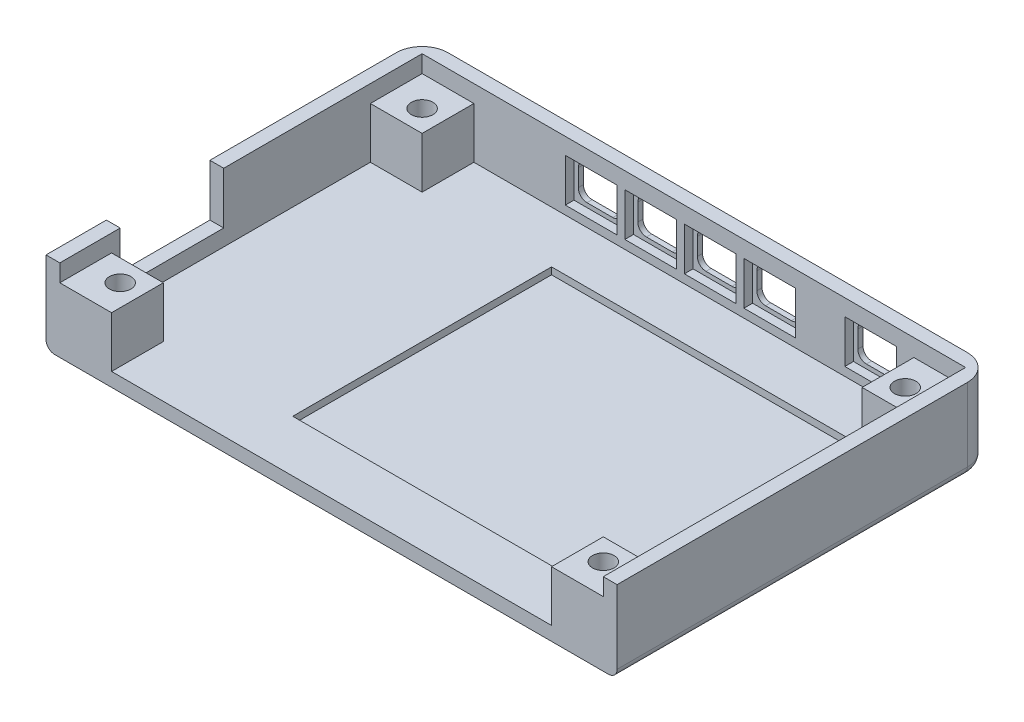
SolidWorks part; units mm, degrees
ref_plane "前视基准面" through (0, 0, 0) normal (0, 0, 1) x (1, 0, 0)
ref_plane "上视基准面" through (0, 0, 0) normal (0, 1, 0) x (1, 0, 0)
ref_plane "右视基准面" through (0, 0, 0) normal (1, 0, 0) x (0, 0, -1)
sketch "草图1" plane through (0, 0, 0) normal (0, 1, 0) x (1, 0, 0)
  line L1 (-31.5, -21) -> (31.5, -21)
  line L2 (-31.5, -21) -> (-31.5, 21)
  line L3 (-31.5, 21) -> (31.5, 21)
  line L4 (31.5, -21) -> (31.5, 21)
  line L5 (-31.5, -21) -> (31.5, 21) construction
  line L6 (-31.5, 21) -> (31.5, -21) construction
  point P0 (0, 0)
  dimension "D1" = 63
  dimension "D2" = 42
extrude "底" add sketch "草图1" against normal blind 1.6
sketch "草图2" plane through (0, 0, 0) normal (0, 1, 0) x (1, 0, 0)
  line L1 (-10.5, -15) -> (31.5, -15)
  line L2 (-10.5, -15) -> (-10.5, 15)
  line L3 (-10.5, 15) -> (31.5, 15)
  line L4 (31.5, -15) -> (31.5, 15)
  line L5 (-10.5, -15) -> (31.5, 15) construction
  line L6 (-10.5, 15) -> (31.5, -15) construction
  line L7 (31.5, 21) -> (-31.5, 21) construction
  line L8 (-31.5, -21) -> (31.5, -21) construction
  line L9 (31.5, -21) -> (31.5, 21) construction
  point P0 (0, 0)
  dimension "D1" = 42
  dimension "D2" = 6
  dimension "D3" = 0
  dimension "D4" = 6
extrude "电池槽" cut sketch "草图2" against normal blind 0.8
sketch "草图4" plane through (0, -1.6, 0) normal (0, -1, 0) x (-1, 0, 0)
  line L0 (-31.5, 21) -> (-31.5, -21)
  line L1 (-31.5, 21) -> (-33.1, 21)
  line L2 (-31.5, -21) -> (-33.1, -21)
  line L3 (-33.1, 21) -> (-33.1, -21)
  line L4 (31.5, 21) -> (31.5, -21)
  line L5 (31.5, 21) -> (33.1, 21)
  line L6 (31.5, -21) -> (33.1, -21)
  line L7 (33.1, 21) -> (33.1, -21)
  dimension "D1" = 1.6
  dimension "D2" = 1.6
extrude "侧边" add sketch "草图4" against normal blind 9.5
sketch "草图5" plane through (0, 0, 0) normal (0, 1, 0) x (1, 0, 0)
  line L0 (-31.5, 21) -> (-31.5, 15)
  line L1 (-31.5, 21) -> (-25.5, 21)
  line L2 (-31.5, 15) -> (-25.5, 15)
  line L3 (-25.5, 21) -> (-25.5, 15)
  line L4 (-31.5, 21) -> (-31.5, -21) construction
  line L5 (25.5, 21) -> (25.5, 15)
  line L6 (25.5, 21) -> (31.5, 21)
  line L7 (25.5, 15) -> (31.5, 15)
  line L8 (31.5, 21) -> (31.5, 15)
  line L9 (-31.5, -15) -> (-31.5, -21)
  line L10 (-31.5, -15) -> (-25.5, -15)
  line L11 (-31.5, -21) -> (-25.5, -21)
  line L12 (-25.5, -15) -> (-25.5, -21)
  line L13 (25.5, -15) -> (25.5, -21)
  line L14 (25.5, -15) -> (31.5, -15)
  line L15 (25.5, -21) -> (31.5, -21)
  line L16 (31.5, -15) -> (31.5, -21)
  dimension "D1" = 6
  dimension "D2" = 6
  dimension "D3" = 6
  dimension "D4" = 6
extrude "螺丝固定" add sketch "草图5" along normal offset from surface (5.9 mm away) 2 up to face at (-32.3, 7.9, 0)
sketch "草图6" plane through (0, 7.9, 0) normal (0, 1, 0) x (1, 0, 0)
  line L0 (-25.5, 15) -> (-25.5, 21) construction
  line L1 (-31.5, 15) -> (-25.5, 15) construction
  circle A0 centre (-28, 17.5) radius 1.25
  circle A1 centre (28, 17.5) radius 1.25
  circle A2 centre (28, -17.5) radius 1.25
  circle A3 centre (-28, -17.5) radius 1.25
  dimension "D1" = 2.5
  dimension "D2" = 2.5
  dimension "D3" = 2.5
  dimension "D4" = 2
  dimension "D5" = 2
extrude "螺丝孔" cut sketch "草图6" against normal up to surface (7.9 mm away) up to face at (-7, 0, 0)
sketch "草图8" plane through (0, 0, 0) normal (0, 1, 0) x (1, 0, 0)
  line L0 (25.5, 21) -> (25.5, 15) construction
  line L1 (-30.5, 20) -> (-25.5, 20)
  line L2 (-30.5, 20) -> (-30.5, 15)
  line L3 (-30.5, 15) -> (-25.5, 15)
  line L4 (-25.5, 20) -> (-25.5, 15)
  line L5 (-30.5, 20) -> (-25.5, 15) construction
  line L6 (-30.5, 15) -> (-25.5, 20) construction
  line L7 (30.5, 20) -> (25.5, 20)
  line L8 (30.5, 20) -> (30.5, 15)
  line L9 (30.5, 15) -> (25.5, 15)
  line L10 (25.5, 20) -> (25.5, 15)
  line L11 (30.5, 20) -> (25.5, 15) construction
  line L12 (30.5, 15) -> (25.5, 20) construction
  line L14 (-30.5, -20) -> (-25.5, -20)
  line L15 (-30.5, -20) -> (-30.5, -15)
  line L16 (-30.5, -15) -> (-25.5, -15)
  line L17 (-25.5, -20) -> (-25.5, -15)
  line L18 (-30.5, -20) -> (-25.5, -15) construction
  line L19 (-30.5, -15) -> (-25.5, -20) construction
  line L20 (30.5, -20) -> (25.5, -20)
  line L21 (30.5, -20) -> (30.5, -15)
  line L22 (30.5, -15) -> (25.5, -15)
  line L23 (25.5, -20) -> (25.5, -15)
  line L24 (30.5, -20) -> (25.5, -15) construction
  line L25 (30.5, -15) -> (25.5, -20) construction
  circle A0 centre (28, 17.5) radius 1.25 construction
  circle A1 centre (28, -17.5) radius 1.25 construction
  circle A2 centre (-28, -17.5) radius 1.25 construction
  circle A3 centre (-28, 17.5) radius 1.25 construction
  circle A4 centre (28, 17.5) radius 1.25 construction
  circle A5 centre (28, -17.5) radius 1.25 construction
  circle A6 centre (-28, -17.5) radius 1.25 construction
  circle A7 centre (-28, 17.5) radius 1.25 construction
sketch "草图9" plane through (0, 0, -21) normal (0, 0, -1) x (-1, 0, 0)
  line L0 (-33.1, 7.9) -> (-33.1, -1.6)
  line L1 (-33.1, 7.9) -> (33.1, 7.9)
  line L2 (-33.1, -1.6) -> (33.1, -1.6)
  line L3 (33.1, 7.9) -> (33.1, -1.6)
extrude "凸台-拉伸4" add sketch "草图9" along normal blind 1.6
sketch "草图10" plane through (0, 0, -21) normal (0, 0, 1) x (1, 0, 0)
  line L1 (17.5, 1) -> (23.5, 1)
  line L2 (17.5, 1) -> (17.5, 6)
  line L3 (17.5, 6) -> (23.5, 6)
  line L4 (23.5, 1) -> (23.5, 6)
  line L5 (17.5, 1) -> (23.5, 6) construction
  line L6 (17.5, 6) -> (23.5, 1) construction
  line L7 (25.5, 0) -> (-25.5, 0) construction
  line L8 (25.5, 5.9) -> (25.5, 0) construction
  line L9 (5.8, 1) -> (11.8, 1)
  line L10 (5.8, 1) -> (5.8, 6)
  line L11 (5.8, 6) -> (11.8, 6)
  line L12 (11.8, 1) -> (11.8, 6)
  line L13 (5.8, 1) -> (11.8, 6) construction
  line L14 (5.8, 6) -> (11.8, 1) construction
  line L15 (-1.1, 1) -> (4.9, 1)
  line L16 (-1.1, 1) -> (-1.1, 6)
  line L17 (-1.1, 6) -> (4.9, 6)
  line L18 (4.9, 1) -> (4.9, 6)
  line L19 (-1.1, 1) -> (4.9, 6) construction
  line L20 (-1.1, 6) -> (4.9, 1) construction
  line L21 (-8, 1) -> (-2, 1)
  line L22 (-8, 1) -> (-8, 6)
  line L23 (-8, 6) -> (-2, 6)
  line L24 (-2, 1) -> (-2, 6)
  line L25 (-8, 1) -> (-2, 6) construction
  line L26 (-8, 6) -> (-2, 1) construction
  line L27 (-14.9, 1) -> (-8.9, 1)
  line L28 (-14.9, 1) -> (-14.9, 6)
  line L29 (-14.9, 6) -> (-8.9, 6)
  line L30 (-8.9, 1) -> (-8.9, 6)
  line L31 (-14.9, 1) -> (-8.9, 6) construction
  line L32 (-14.9, 6) -> (-8.9, 1) construction
  point P0 (20.5, 3.5)
  point P11 (8.8, 3.5)
  point P16 (1.9, 3.5)
  point P21 (-5, 3.5)
  point P26 (-11.9, 3.5)
  dimension "D1" = 6
  dimension "D2" = 5
  dimension "D3" = 5
  dimension "D4" = 3.5
  dimension "D5" = 2
  dimension "D6" = 4
extrude "按键底" cut sketch "草图10" against normal blind 1
sketch "草图12" plane through (0, 0, -22) normal (0, 0, 1) x (1, 0, 0)
  line L0 (17.5, 6) -> (23.5, 1) construction
  line L1 (6.3, 2.5) -> (6.3, 4.5)
  line L2 (19, 1.5) -> (22, 1.5)
  line L3 (18, 2.5) -> (18, 4.5)
  line L4 (23.5, 1) -> (23.5, 6)
  line L5 (23.5, 6) -> (17.5, 6)
  line L6 (17.5, 6) -> (17.5, 1)
  line L7 (17.5, 1) -> (23.5, 1)
  line L8 (23.5, 1) -> (23.5, 6) construction
  line L9 (23.5, 6) -> (17.5, 6) construction
  line L10 (17.5, 6) -> (17.5, 1) construction
  line L11 (17.5, 1) -> (23.5, 1) construction
  line L12 (19, 5.5) -> (22, 5.5)
  line L13 (23, 2.5) -> (23, 4.5)
  line L14 (18, 1.5) -> (23, 5.5) construction
  line L15 (18, 5.5) -> (23, 1.5) construction
  line L16 (7.3, 1.5) -> (10.3, 1.5)
  line L17 (7.3, 5.5) -> (10.3, 5.5)
  line L18 (11.3, 2.5) -> (11.3, 4.5)
  line L19 (-0.6, 2.5) -> (-0.6, 4.5)
  line L20 (0.4, 1.5) -> (3.4, 1.5)
  line L21 (0.4, 5.5) -> (3.4, 5.5)
  line L22 (4.4, 2.5) -> (4.4, 4.5)
  line L23 (-7.5, 2.5) -> (-7.5, 4.5)
  line L24 (-6.5, 1.5) -> (-3.5, 1.5)
  line L25 (-6.5, 5.5) -> (-3.5, 5.5)
  line L26 (-2.5, 2.5) -> (-2.5, 4.5)
  line L27 (-14.4, 2.5) -> (-14.4, 4.5)
  line L28 (-13.4, 1.5) -> (-10.4, 1.5)
  line L29 (-13.4, 5.5) -> (-10.4, 5.5)
  line L30 (-9.4, 2.5) -> (-9.4, 4.5)
  arc A0 (22, 5.5) -> (23, 4.5) centre (22, 4.5) cw
  arc A1 (22, 1.5) -> (23, 2.5) centre (22, 2.5) ccw
  arc A2 (19, 1.5) -> (18, 2.5) centre (19, 2.5) cw
  arc A3 (18, 4.5) -> (19, 5.5) centre (19, 4.5) cw
  arc A4 (6.3, 4.5) -> (7.3, 5.5) centre (7.3, 4.5) cw
  arc A5 (7.3, 1.5) -> (6.3, 2.5) centre (7.3, 2.5) cw
  arc A6 (10.3, 5.5) -> (11.3, 4.5) centre (10.3, 4.5) cw
  arc A7 (10.3, 1.5) -> (11.3, 2.5) centre (10.3, 2.5) ccw
  arc A8 (-0.6, 4.5) -> (0.4, 5.5) centre (0.4, 4.5) cw
  arc A9 (0.4, 1.5) -> (-0.6, 2.5) centre (0.4, 2.5) cw
  arc A10 (3.4, 5.5) -> (4.4, 4.5) centre (3.4, 4.5) cw
  arc A11 (3.4, 1.5) -> (4.4, 2.5) centre (3.4, 2.5) ccw
  arc A12 (-7.5, 4.5) -> (-6.5, 5.5) centre (-6.5, 4.5) cw
  arc A13 (-6.5, 1.5) -> (-7.5, 2.5) centre (-6.5, 2.5) cw
  arc A14 (-3.5, 5.5) -> (-2.5, 4.5) centre (-3.5, 4.5) cw
  arc A15 (-3.5, 1.5) -> (-2.5, 2.5) centre (-3.5, 2.5) ccw
  arc A16 (-14.4, 4.5) -> (-13.4, 5.5) centre (-13.4, 4.5) cw
  arc A17 (-13.4, 1.5) -> (-14.4, 2.5) centre (-13.4, 2.5) cw
  arc A18 (-10.4, 5.5) -> (-9.4, 4.5) centre (-10.4, 4.5) cw
  arc A19 (-10.4, 1.5) -> (-9.4, 2.5) centre (-10.4, 2.5) ccw
  point P2 (20.5, 3.5)
  dimension "D4" = 1
  dimension "D2" = 5
  dimension "D3" = 4
  dimension "D1" = 0
  dimension "D5" = 2
  dimension "D6" = 4
extrude "按键头" cut sketch "草图12" against normal up to next
fillet "圆角4" radius 1 3 edges at (-33.1, -1.6, -0.8) (33.1, -1.6, -0.8) (0, -1.6, -22.6)
fillet "圆角5" radius 3 4 edges at (-32.8071, -1.3071, -22.3071) (32.8071, -1.3071, -22.3071) (33.1, 3.65, -22.6) (-33.1, 3.65, -22.6)
sketch "草图15" plane through (0, 7.9, 0) normal (0, 1, 0) x (1, 0, 0)
  line L16 (33.1, -21) -> (33.1, 19.6)
  line L17 (30.1, 22.6) -> (-30.1, 22.6)
  line L18 (-33.1, 19.6) -> (-33.1, -21)
  line L19 (-33.1, -21) -> (-31.5, -21)
  line L22 (-31.5, -21) -> (-31.5, 21)
  line L25 (-31.5, 21) -> (31.5, 21)
  line L28 (31.5, 21) -> (31.5, -21)
  line L31 (31.5, -21) -> (33.1, -21)
  line L32 (33.1, -21) -> (33.1, 19.6)
  line L33 (30.1, 22.6) -> (-30.1, 22.6)
  line L34 (-33.1, 19.6) -> (-33.1, -21)
  line L35 (-33.1, -21) -> (-31.5, -21)
  line L38 (-31.5, -21) -> (-31.5, 21)
  line L41 (-31.5, 21) -> (31.5, 21)
  line L44 (31.5, 21) -> (31.5, -21)
  line L47 (31.5, -21) -> (33.1, -21)
  arc A2 (33.1, 19.6) -> (30.1, 22.6) centre (30.1, 19.6) ccw
  arc A3 (-30.1, 22.6) -> (-33.1, 19.6) centre (-30.1, 19.6) ccw
  arc A4 (33.1, 19.6) -> (30.1, 22.6) centre (30.1, 19.6) ccw
  arc A5 (-30.1, 22.6) -> (-33.1, 19.6) centre (-30.1, 19.6) ccw
  dimension "D1" = 0
sketch "草图16" plane through (-31.5, 0, 0) normal (1, 0, 0) x (0, 0, -1)
  line L0 (-14, 7.9) -> (-2, 7.9)
  line L1 (-14, 7.9) -> (-14, 1.9)
  line L2 (-2, 7.9) -> (-2, 1.9)
  line L3 (-14, 1.9) -> (-2, 1.9)
  line L4 (-21, 7.9) -> (21, 7.9) construction
  line L5 (-15, 5.9) -> (-15, 0) construction
  dimension "D1" = 12
  dimension "D2" = 6
  dimension "D3" = 1
extrude "tf口" cut sketch "草图16" against normal up to next
